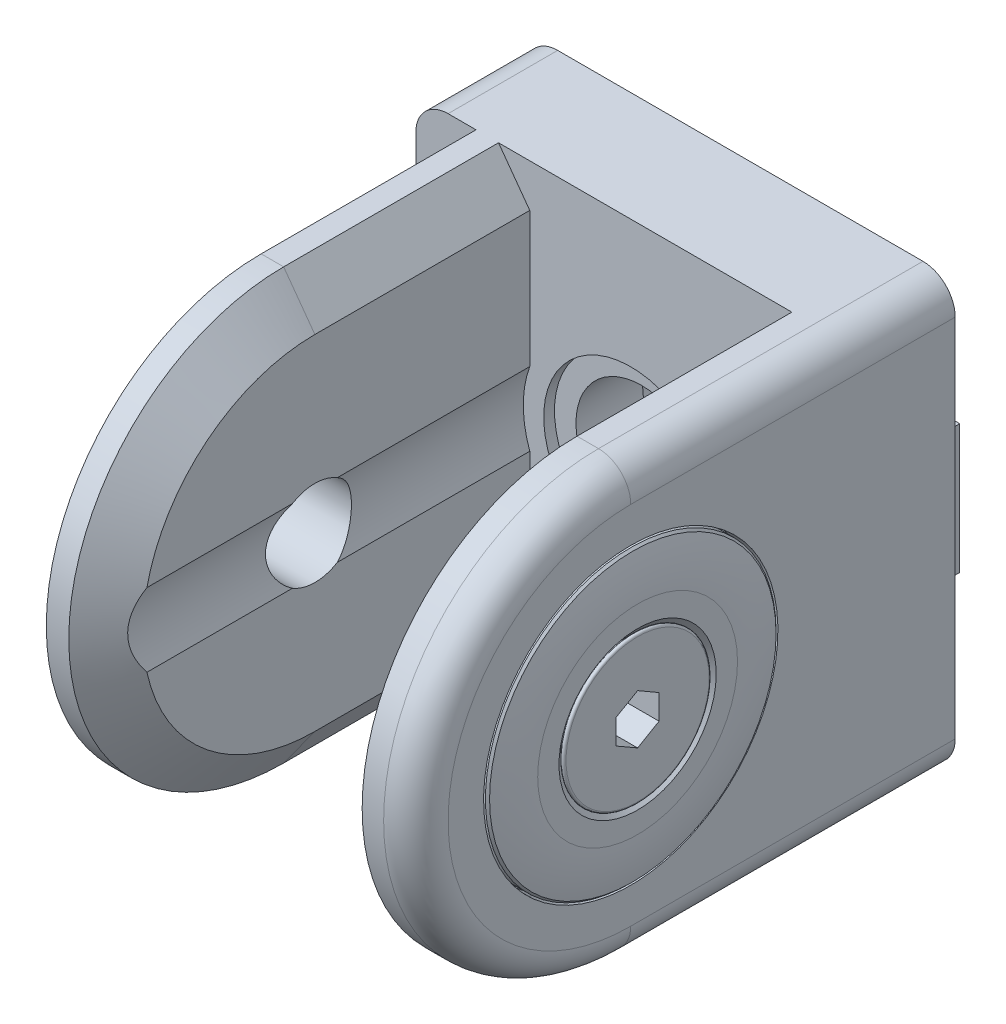
SolidWorks part; units mm, degrees
ref_plane "Спереди" through (0, 0, 0) normal (0, 0, 1) x (1, 0, 0)
ref_plane "Сверху" through (0, 0, 0) normal (0, 1, 0) x (1, 0, 0)
ref_plane "Справа" through (0, 0, 0) normal (1, 0, 0) x (0, 0, -1)
sketch "Sketch1" plane through (0, 0, 0) normal (0, 0, 1) x (1, 0, 0)
  line L1 (-10, 10) -> (10, 10)
  line L2 (-10, 10) -> (-10, -10)
  line L3 (-10, -10) -> (10, -10)
  line L4 (10, 10) -> (10, -10)
  line L5 (-10, 10) -> (10, -10) construction
  line L6 (-10, -10) -> (10, 10) construction
  circle A0 centre (0, 0) radius 3.05
  point P0 (0, 0)
  dimension "D2" = 6.1
  dimension "D1" = 20
extrude "Extrude1" add sketch "Sketch1" along normal blind 5.1
sketch "Sketch2" plane through (10, 0, 0) normal (1, 0, 0) x (0, 0, -1)
  line L0 (-15.1, 13.4341) -> (-15.1, -14.3338) construction
  line L1 (-5.1, -10) -> (-5.1, 10) construction
  line L2 (-5.1, 0) -> (-25.1, 0) construction
  line L3 (-5.1, 10) -> (-15.1, 10)
  line L4 (-5.1, -10) -> (-15.1, -10)
  line L5 (-5.1, 10) -> (-5.1, -10)
  circle A0 centre (-15.1, 0) radius 2
  arc A1 (-15.1, 10) -> (-15.1, -10) centre (-15.1, 0) ccw
  dimension "D3" = 4
  dimension "D1" = 10
extrude "Extrude2" add sketch "Sketch2" against normal blind 2.5
fillet "Fillet1" radius 1.5 5 edges at (10, 10, 7.55) (10, -10, 7.55) (10, 0, 25.1) (-10, -10, 2.55) (-10, 10, 2.55)
extrude "Extrude3" add sketch "Sketch" along normal blind 2.5 from offset 17.2 offset against normal yes
sketch "Sketch" plane through (10, 0, 0) normal (1, 0, 0) x (0, 0, -1) same geometry as "Sketch2"
chamfer "Chamfer3" distance 2 angle 36 3 edges at (-4.7, -10, 10.1) (-4.7, 0, 25.1) (-4.7, 10, 10.1) first distance on face at (-4.7, 0, 12.6)
sketch "Sketch3" plane through (0, 0, 5.1) normal (0, 0, 1) x (1, 0, 0)
  circle A2 centre (0, 0) radius 4.05
  circle A3 centre (0, 0) radius 4.05
  dimension "D1" = 1
extrude "Extrude4" cut sketch "Sketch3" against normal blind 0.5
sketch "Sketch10" plane through (0, 0, 5.1) normal (0, 0, 1) x (1, 0, 0)
  circle A0 centre (0, 0) radius 5
  dimension "D1" = 10
extrude "Extrude10" cut sketch "Sketch10" along normal through all
sketch "Sketch4" plane through (0, 0, 0) normal (0, 0, -1) x (-1, 0, 0)
  line L0 (-7.5, 10) -> (6.1531, 10) construction
  line L1 (-3.1, 9) -> (3.1, 9)
  line L2 (-3.1, 9) -> (-3.1, 4.65)
  line L3 (-3.1, 4.65) -> (3.1, 4.65)
  line L4 (3.1, 9) -> (3.1, 4.65)
  line L5 (-3.1, 9) -> (3.1, 4.65) construction
  line L6 (-3.1, 4.65) -> (3.1, 9) construction
  line L7 (9, 3.1) -> (9, -3.1)
  line L8 (9, 3.1) -> (4.65, 3.1)
  line L9 (4.65, 3.1) -> (4.65, -3.1)
  line L10 (9, -3.1) -> (4.65, -3.1)
  line L11 (9, 3.1) -> (4.65, -3.1) construction
  line L12 (4.65, 3.1) -> (9, -3.1) construction
  line L13 (3.1, -9) -> (-3.1, -9)
  line L14 (3.1, -9) -> (3.1, -4.65)
  line L15 (3.1, -4.65) -> (-3.1, -4.65)
  line L16 (-3.1, -9) -> (-3.1, -4.65)
  line L17 (3.1, -9) -> (-3.1, -4.65) construction
  line L18 (3.1, -4.65) -> (-3.1, -9) construction
  line L19 (-9, -3.1) -> (-9, 3.1)
  line L20 (-9, -3.1) -> (-4.65, -3.1)
  line L21 (-4.65, -3.1) -> (-4.65, 3.1)
  line L22 (-9, 3.1) -> (-4.65, 3.1)
  line L23 (-9, -3.1) -> (-4.65, 3.1) construction
  line L24 (-4.65, -3.1) -> (-9, 3.1) construction
  line L25 (-3.1, 6.0648) -> (-6.0648, 3.1)
  line L26 (6.0648, 3.1) -> (3.1, 6.0648)
  line L27 (3.1, -6.0648) -> (6.0648, -3.1)
  line L28 (-6.0648, -3.1) -> (-3.1, -6.0648)
  point P0 (0, 6.825)
  point P5 (-0.6735, 10)
  point P12 (6.825, 0)
  point P17 (0, -6.825)
  point P22 (-6.825, 0)
  point P27 (0, 0)
  point P36 (0, 0)
  circle M5 centre (0, 0) radius 3.05
  dimension "D1" = 6.2
  dimension "D2" = 4.35
  dimension "D3" = 1
  dimension "D4" = 4
  dimension "D5" = 4
extrude "Extrude5" cut sketch "Sketch4" against normal blind 3 contours L4 L1 L2 L3 | L22 L19 L20 L21 | L10 L7 L8 L9 | L16 L13 L14 L15 region at (0, 6.825, 0) region at (6.825, 0, 0) region at (-6.825, 0, 0) region at (0, -6.825, 0)
extrude "Extrude6" cut sketch "Sketch" against normal blind 1.5 contours L20 L28 L16 L15 L14 L27 L10 L9 L8 L26 L4 L3 L2 L25 L22 L21 M5 region at (3.2715, 5.3574, 0)
sketch "Sketch" plane through (0, 0, 0) normal (0, 0, -1) x (-1, 0, 0) same geometry as "Sketch4"
sketch "Sketch5" plane through (-7.2, 0, 0) normal (-1, 0, 0) x (0, 0, 1)
  circle A2 centre (15.1, 0) radius 4
  circle A3 centre (15.1, 0) radius 4
  circle M6 centre (15.1, 0) radius 2
  dimension "D1" = 2
extrude "Extrude7" add sketch "Sketch5" along normal blind 1.5 contours A3 M6 region at (-7.2, 0, 11.2131)
sketch "Sketch12" plane through (0, 0, 1.5) normal (0, 0, -1) x (-1, 0, 0)
  line L8 (3, 4.75) -> (3, 8.9)
  line L9 (3, 8.9) -> (-3, 8.9)
  line L10 (-3, 8.9) -> (-3, 4.75)
  line L11 (-3, 4.75) -> (3, 4.75)
  line L12 (3, 4.75) -> (3, 8.9)
  line L13 (3, 8.9) -> (-3, 8.9)
  line L14 (-3, 8.9) -> (-3, 4.75)
  line L15 (-3, 4.75) -> (3, 4.75)
  line L20 (-3, -4.75) -> (-3, -8.9)
  line L21 (-3, -8.9) -> (3, -8.9)
  line L22 (3, -8.9) -> (3, -4.75)
  line L23 (3, -4.75) -> (-3, -4.75)
  line L24 (-3, -4.75) -> (-3, -8.9)
  line L25 (-3, -8.9) -> (3, -8.9)
  line L26 (3, -8.9) -> (3, -4.75)
  line L27 (3, -4.75) -> (-3, -4.75)
  line L40 (-5.8234, 3.2) -> (-5.8234, -3.2)
  line L41 (5.8234, 3.2) -> (5.8234, -3.2)
  line L56 (-4.55, -3.2) -> (-5.8234, -3.2)
  line L57 (-5.8234, -3.2) -> (-3.2, -5.8234)
  line L58 (-3.2, -5.8234) -> (-3.2, -4.55)
  line L59 (-3.2, -4.55) -> (3.2, -4.55)
  line L60 (3.2, -4.55) -> (3.2, -5.8234)
  line L61 (3.2, -5.8234) -> (5.8234, -3.2)
  line L62 (5.8234, -3.2) -> (4.55, -3.2)
  line L63 (4.55, -3.2) -> (4.55, 3.2)
  line L64 (4.55, 3.2) -> (5.8234, 3.2)
  line L65 (5.8234, 3.2) -> (3.2, 5.8234)
  line L66 (3.2, 5.8234) -> (3.2, 4.55)
  line L67 (3.2, 4.55) -> (-3.2, 4.55)
  line L68 (-3.2, 4.55) -> (-3.2, 5.8234)
  line L69 (-3.2, 5.8234) -> (-5.8234, 3.2)
  line L70 (-5.8234, 3.2) -> (-4.55, 3.2)
  line L71 (-4.55, 3.2) -> (-4.55, -3.2)
  line L73 (-5.8234, -3.2) -> (-3, -6.0234)
  line L77 (3, -6.0234) -> (5.8234, -3.2)
  line L81 (5.8234, 3.2) -> (3, 6.0234)
  line L85 (-3, 6.0234) -> (-5.8234, 3.2)
  circle A2 centre (0, 0) radius 3.15
  circle A3 centre (0, 0) radius 3.15
  line M27 (-4.65, -3.1) -> (-6.0648, -3.1)
  line M29 (-3.1, -6.0648) -> (-3.1, -4.65)
  line M30 (-3.1, -4.65) -> (3.1, -4.65)
  line M31 (3.1, -4.65) -> (3.1, -6.0648)
  line M33 (6.0648, -3.1) -> (4.65, -3.1)
  line M34 (4.65, -3.1) -> (4.65, 3.1)
  line M35 (4.65, 3.1) -> (6.0648, 3.1)
  line M37 (3.1, 6.0648) -> (3.1, 4.65)
  line M38 (3.1, 4.65) -> (-3.1, 4.65)
  line M39 (-3.1, 4.65) -> (-3.1, 6.0648)
  line M41 (-6.0648, 3.1) -> (-4.65, 3.1)
  line M42 (-4.65, 3.1) -> (-4.65, -3.1)
  dimension "D1" = 0.1
  dimension "D2" = 0.1
  dimension "D3" = 0.1
  dimension "D4" = 0.1
extrude "Extrude11" add sketch "Sketch12" along normal blind 1.4 from offset 0.01 separate body contours L85 L40 L73 L77 L41 L81 A3 M39 M41 M42 M27 M29 M30 M31 M33 M34 M35 M37 M38 | L40 M41 M27 M42 | L41 M35 M34 M33 | L14 L85 L81 L12 L15 M39 M38 M37 | L26 L77 L73 L24 L27 M31 M30 M29 region at (-3.0635, 5.3867, 1.5) region at (-3.1037, 5.8271, 1.5) region at (-4.3952, 4.3952, 1.5) region at (-5.7581, 3.15, 1.5) region at (-5.2367, 0, 1.5) region at (5.1867, 3.1347, 1.5) region at (5.2367, 0, 1.5) region at (-3.1037, -5.8271, 1.5) region at (-3.0051, -5.9285, 1.5)
extrude "Extrude12" add sketch "Sketch" against normal blind 1.4 and the other way blind 2.8 from offset 0.01 contours L14 L15 L12 L13 | L26 L27 L24 L25 region at (0, 6.825, 1.5) region at (0, -6.825, 1.5)
sketch "Sketch" plane through (0, 0, 1.5) normal (0, 0, -1) x (-1, 0, 0) same geometry as "Sketch12"
sketch "Sketch6" plane through (10, 0, 0) normal (1, 0, 0) x (0, 0, -1)
  circle A0 centre (-15.1, 0) radius 6.85
  dimension "D1" = 13.7
extrude "Extrude8" cut sketch "Sketch6" against normal blind 1
chamfer "Chamfer1" distance 4.8 angle 45 1 edges at (9, 2, 15.1)
sketch "Sketch7" plane through (0, 0, 0) normal (0, 1, 0) x (1, 0, 0)
  line L0 (14.3348, -15.1) -> (3.7107, -15.1) construction
  line L1 (10, -8.3364) -> (10.0964, -8.4328)
  line L2 (10, -21.95) -> (10, -8.25) construction
  line L3 (10.3196, -10.4503) -> (10.3196, -11.4417)
  line L4 (10.3196, -11.4417) -> (8.7407, -13.0205)
  line L5 (8.7407, -13.0205) -> (8.7407, -11.0823)
  line L6 (8.7407, -11.0823) -> (7.3532, -11.0823)
  line L7 (7.3532, -11.0823) -> (7.3532, -9.9832)
  line L8 (7.3532, -9.9832) -> (9, -8.3364)
  line L9 (9, -21.95) -> (9, -8.25) construction
  line L10 (9, -8.3364) -> (10, -8.3364)
  line L11 (10.3196, -15.1) -> (10.3196, -11.7683)
  line L12 (-6.1531, -5.1) -> (7.5, -5.1) construction
  line L13 (10.1489, -11.6976) -> (8.7465, -13.1)
  line L14 (8.7465, -13.1) -> (5.086, -13.1)
  line L15 (5.086, -13.1) -> (4.8151, -13.3709)
  line L16 (4.8151, -13.3709) -> (4.8151, -15.1)
  line L17 (4.8151, -15.1) -> (10.3196, -15.1)
  arc A0 (10.3196, -11.7683) -> (10.1489, -11.6976) centre (10.2196, -11.7683) ccw
  arc A1 (10.0964, -8.4328) -> (10.3196, -10.4503) centre (1.0902, -10.4503) cw
  dimension "D3" = 0.1
  dimension "D1" = 135
  dimension "D2" = 135
  dimension "D4" = 2
  dimension "D5" = 10
  dimension "D6" = 45
revolve "Revolve1" add sketch "Sketch7" angle 360 about L0
ref_axis "Axis1" through (-4.7, 0, 15.1) along (-1, 0, 0)
sketch "Sketch8" plane through (10.3196, 0, 0) normal (1, 0, 0) x (0, 0, -1)
  line L1 (-15.1, 1.1547) -> (-16.1, 0.5774)
  line L2 (-16.1, 0.5774) -> (-16.1, -0.5774)
  line L3 (-16.1, -0.5774) -> (-15.1, -1.1547)
  line L4 (-15.1, -1.1547) -> (-14.1, -0.5774)
  line L5 (-14.1, -0.5774) -> (-14.1, 0.5774)
  line L6 (-14.1, 0.5774) -> (-15.1, 1.1547)
  circle A0 centre (-15.1, 0) radius 1 construction
  dimension "D1" = 2
extrude "Extrude9" cut sketch "Sketch8" against normal blind 2.2
chamfer "Chamfer2" distance 0.5 angle 45 6 edges at (8.1196, 0, 14.1) (8.1196, -0.866, 14.6) (8.1196, -0.866, 15.6) (8.1196, 0, 16.1) (8.1196, 0.866, 15.6) (8.1196, 0.866, 14.6)
move or copy body "Both_inserts_rotate" [suppressed] bodies to move or copy 121 copy no rotation origin (0, 0, 0) rotation axis (0, 0, 1) rotation angle 90
pattern_circular "Angle" [suppressed] count 2 over 90 about axis through (-4.7, 0, 15.1) along (-1, 0, 0) of bodies 121 110 111
ref_axis "Axis2" [suppressed] through (0, -10.5, 15.1) along (0, -1, 0)
move or copy body "Body-Move/Copy1" [suppressed] bodies to move or copy 113 copy no rotation origin (0, 0, 15.1) rotation axis (0, 1, 0) rotation angle 180
mirror "Mirror1" [suppressed] about plane through (0, 0, 0) normal (1, 0, 0) of bodies 111 118 116
move or copy body "One_insert_rotate" bodies to move or copy 121 copy no rotation origin (0, 0, 0) rotation axis (0, 0, 1) rotation angle 90
equation "\"Angle\"= 90"
equation "\"D3@Angle\"= \"Angle\""
